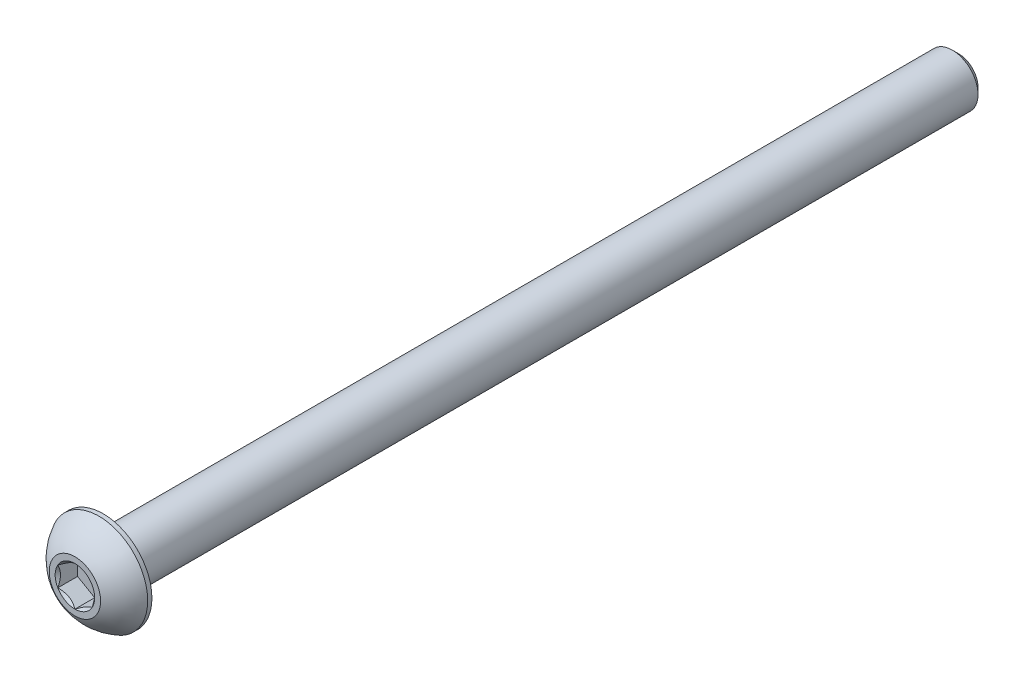
SolidWorks part; units mm, degrees
ref_plane "Front" through (0, 0, 0) normal (0, 0, 1) x (1, 0, 0)
ref_plane "Top" through (0, 0, 0) normal (0, 1, 0) x (1, 0, 0)
ref_plane "Right" through (0, 0, 0) normal (1, 0, 0) x (0, 0, -1)
sketch "Sketch1" plane through (0, 0, 0) normal (1, 0, 0) x (0, 0, -1)
  line L2 (1.65, 1.5) -> (51.65, 1.5)
  line L3 (51.65, 1.5) -> (51.65, 0)
  line L4 (51.65, 0) -> (1.65, 0)
  line L6 (1.4025, 2.85) -> (1.65, 2.85) construction
  line L7 (51.65, 1.5) -> (51.65, -1.5) construction
  line L8 (0, 0) -> (1.65, 0) construction
  line L9 (1.65, 2.85) -> (1.65, -2.85) construction
  line L11 (1.65, 1.5) -> (1.65, 0)
  line L13 (0, 1) -> (0, -1) construction
  line L14 (0, 1) -> (0, 1.5) construction
  arc A3 (0, 1.5) -> (1.4025, 2.85) centre (2.7948, 0) cw construction
  dimension "D1" = 0.2475
revolve "Revolve1" add sketch "Sketch1" angle 360 mid plane about L4
sketch "Sketch3" plane through (0, 0, -51.65) normal (0, 0, -1) x (-1, 0, 0)
  circle A0 centre (0, 0) radius 1.5
curve "Helix/Spiral1" pitch 0.5 height 50.5 turns 101
chamfer "Chamfer1" distance 0.375 angle 45 1 edges at (0, 1.5, -51.65)
sketch "Sketch7" plane through (0, 0, 0) normal (1, 0, 0) x (0, 0, -1)
  line L6 (1.4025, 2.85) -> (1.65, 2.85) construction
  line L8 (0, 0) -> (1.65, 0) construction
  line L11 (1.65, 2.85) -> (1.65, -2.85) construction
  line L12 (1.4025, 2.85) -> (1.65, 2.85)
  line L13 (0, 0) -> (1.65, 0)
  line L14 (0, 1) -> (0, -1) construction
  line L15 (1.65, 2.85) -> (1.65, 0)
  line L16 (0, 1.5) -> (0, 0)
  arc A2 (1.4025, 2.85) -> (0, 1.5) centre (2.7948, 0) ccw construction
  arc A3 (1.4025, 2.85) -> (0, 1.5) centre (2.7948, 0) ccw
revolve "Revolve2" add sketch "Sketch7" angle 360 mid plane about L13
sketch "Sketch5" plane through (0, 0, 0) normal (0, 0, 1) x (1, 0, 0)
  line L1 (1, -0.5774) -> (1, 0.5774)
  line L2 (1, 0.5774) -> (0, 1.1547)
  line L3 (0, 1.1547) -> (-1, 0.5774)
  line L4 (-1, 0.5774) -> (-1, -0.5774)
  line L5 (-1, -0.5774) -> (0, -1.1547)
  line L6 (0, -1.1547) -> (1, -0.5774)
  circle A0 centre (0, 0) radius 1 construction
extrude "Cut-Extrude2" cut sketch "Sketch5" against normal blind 1.155
sketch "Sketch6" plane through (0, 0, 0) normal (0, 0, 1) x (1, 0, 0)
  circle A0 centre (0, 0) radius 1.1547
extrude "Cut-Extrude3" cut sketch "Sketch6" against normal blind 1.155 draft 45
sketch "Sketch2" plane through (0, 0, 0) normal (1, 0, 0) x (0, 0, -1)
  line L0 (51.275, 1.5) -> (51.7125, 1.5)
  line L1 (51.7125, 1.5) -> (51.525, 1.1752)
  line L2 (51.525, 1.1752) -> (51.4625, 1.1752)
  line L3 (51.4625, 1.1752) -> (51.275, 1.5)
  line L4 (51.3688, 1.3376) -> (51.6188, 1.3376) construction
  dimension "D1" = 60
  dimension "D2" = 0.0625
  dimension "D3" = 0.25
sweep "Cut-Sweep1" [suppressed] cut profiles "Sketch2" path "Helix/Spiral1"
sketch "Sketch10" plane through (0, 0, 0) normal (1, 0, 0) x (0, 0, -1)
  line L0 (51.65, 1.5) -> (51.65, -1.5) construction
  point P0 (50.9, -1.5)
  dimension "D1" = 0.75
ref_axis "Center Axis 1" through (0, 0, -8.1113) along (0, 0, 1)
ref_plane "Contact Plane 1" through (0, 0, -1.65) normal (0, 0, -1) x (-1, 0, 0)
ref_plane "Contact Plane 2" through (0, 0, 0) normal (0, 0, 1) x (1, 0, 0)
equation "\"D3@Helix/Spiral1\" = \"Lg@Sketch1\" + \"D4@Helix/Spiral1\""
equation "\"D2@Sketch2\" = \"D4@Helix/Spiral1\" * .125"
equation "\"D3@Sketch2\" = \"D4@Helix/Spiral1\" * .5"
equation "\"D1@Chamfer1\" = \"D4@Helix/Spiral1\" * .75"
equation "\"D1@Cut-Extrude2\" = \"Head Ht@Sketch1\" * .7"
equation "\"D1@Sketch1\" = \"Head Ht@Sketch1\" * .15"
equation "\"D1@Sketch10\" = \"D4@Helix/Spiral1\" * 1.5"
equation "\"D1@Cut-Extrude3\" = \"D1@Cut-Extrude2\""
